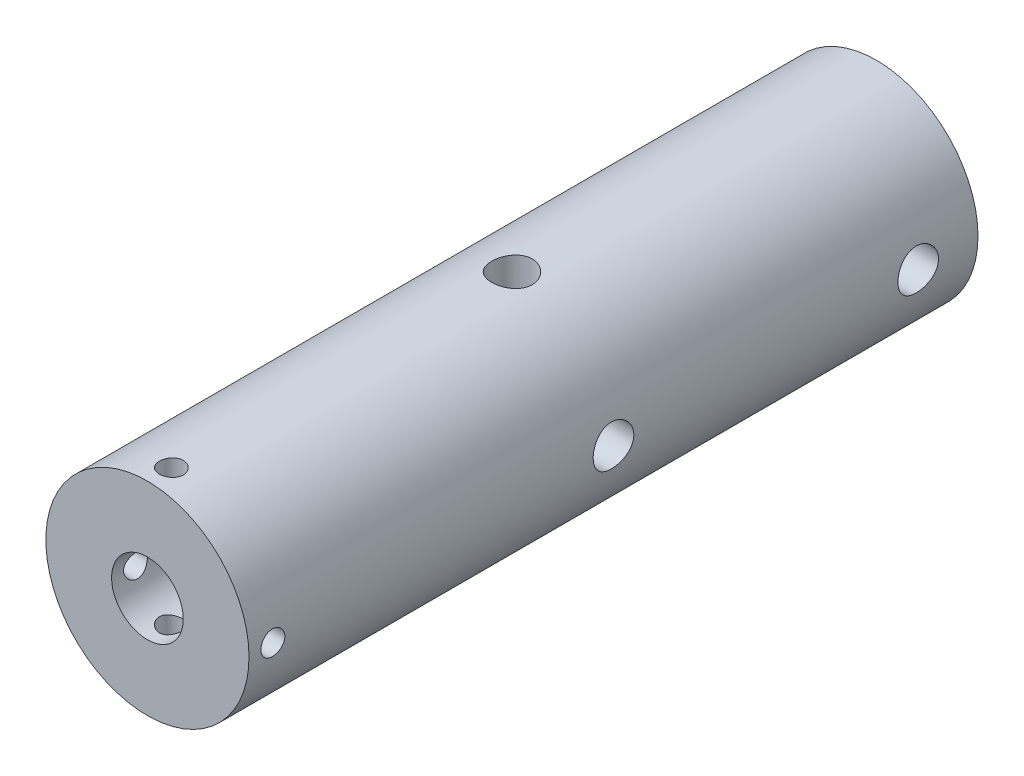
SolidWorks part; units mm, degrees
material "Alumina"
ref_plane "Front Plane" through (0, 0, 0) normal (0, 0, 1) x (1, 0, 0)
ref_plane "Top Plane" through (0, 0, 0) normal (0, 1, 0) x (1, 0, 0)
ref_plane "Right Plane" through (0, 0, 0) normal (1, 0, 0) x (0, 0, -1)
sketch "Sketch1" plane through (0, 0, 0) normal (0, 0, 1) x (1, 0, 0)
  circle A0 centre (0, 0) radius 8.5
  dimension "D1" = 17
extrude "Boss-Extrude1" add sketch "Sketch1" along normal blind 61
ref_plane "Plane1" through (0, 0, 0) normal (1, 0, 0) x (0, 0, -1)
ref_plane "Plane2" through (0, 0, 61) normal (0, 0, 1) x (1, 0, 0)
sketch "Sketch7" plane through (0, 0, 0) normal (1, 0, 0) x (0, 0, -1)
  line L0 (0, 0) -> (-64.6099, 0) construction
  line L1 (-64.6099, 0) -> (5.371, 0) construction
  line L2 (-61, 3) -> (-5, 3)
  line L3 (-61, 8.5) -> (-61, -8.5) construction
  line L4 (-5, 3) -> (-1, 1.5)
  line L5 (-1, 1.5) -> (0, 1.5)
  line L6 (0, -8.5) -> (0, 8.5) construction
  line L7 (0, 1.5) -> (0, 0)
  line L8 (-61, 3) -> (-61, 0)
  line L9 (0, 0) -> (-61, 0)
  point P8 (-0.5, 1.5)
  dimension "D1" = 4
  dimension "D2" = 1
  dimension "D3" = 1.5
  dimension "D4" = 3
revolve "Cut-Revolve1" cut sketch "Sketch7" angle 360 about L0
ref_plane "Plane3" through (8.5, 0, 0) normal (1, 0, 0) x (0, 0, -1)
sketch "Sketch9" plane through (8.5, 0, 0) normal (1, 0, 0) x (0, 0, -1)
  circle A0 centre (-5, 0) radius 1.7
  dimension "D1" = 3.4
  dimension "D2" = 5
extrude "Cut-Extrude2" cut sketch "Sketch9" against normal blind 6.7
sketch "Sketch10" plane through (0, 0, 0) normal (1, 0, 0) x (0, 0, -1)
  line L0 (-61, 8.5) -> (-61, -8.5) construction
  circle A0 centre (-59, 0) radius 1
  dimension "D1" = 2
  dimension "D2" = 2
extrude "Cut-Extrude3" cut sketch "Sketch10" against normal blind 8.7
pattern_circular "CirPattern1" count 4 over 360 about axis through (0, 0, 61) along (0, 0, 1) of "Cut-Extrude3"
ref_plane "Plane4" through (0, 8.5, 0) normal (0, 1, 0) x (1, 0, 0)
sketch "Sketch11" plane through (0, 8.5, 0) normal (0, 1, 0) x (1, 0, 0)
  line L0 (0, 0) -> (0, -61) construction
  line L1 (0, -61) -> (0, -30.5) construction
  line L2 (0, -30.5) -> (12.403, -30.5) construction
  line L3 (12.403, -30.5) -> (-11.7433, -30.5) construction
  circle A0 centre (0, -30.5) radius 1.7
  dimension "D1" = 3.4
  dimension "D2" = 30.5
extrude "Cut-Extrude4" cut sketch "Sketch11" against normal blind 26.7
sketch "Sketch12" plane through (0, 0, 0) normal (1, 0, 0) x (0, 0, -1)
  line L0 (0, 0) -> (-61, 0) construction
  line L1 (-61, 8.5) -> (-61, -8.5) construction
  line L2 (-61, 0) -> (-30.5, 0) construction
  circle A0 centre (-30.5, 0) radius 1.7
  dimension "3" = 3.4
extrude "Cut-Extrude5" cut sketch "Sketch12" against normal blind 10 and the other way blind 10
ref_axis "Axis1" through (0, 0, 0) along (0, 0, 1)
